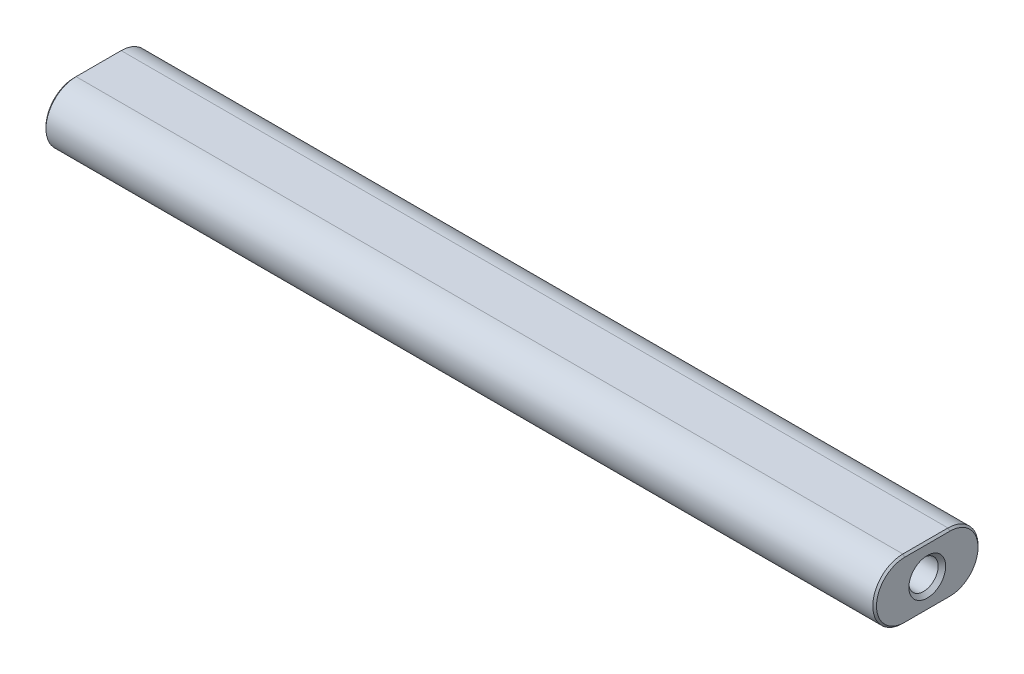
SolidWorks part; units mm, degrees
ref_plane "Front Plane" through (0, 0, 0) normal (0, 0, 1) x (1, 0, 0)
ref_plane "Top Plane" through (0, 0, 0) normal (0, 1, 0) x (1, 0, 0)
ref_plane "Right Plane" through (0, 0, 0) normal (1, 0, 0) x (0, 0, -1)
sketch "Sketch1" plane through (0, 0, 0) normal (1, 0, 0) x (0, 0, -1)
  line L0 (-3, 0) -> (3, 0) construction
  line L1 (-3, 4) -> (3, 4)
  line L2 (-3, -4) -> (3, -4)
  arc A0 (-3, 4) -> (-3, -4) centre (-3, 0) ccw
  arc A1 (3, -4) -> (3, 4) centre (3, 0) ccw
  point P2 (0, 0)
  dimension "D1" = 8
  dimension "D2" = 6
extrude "Boss-Extrude1" add sketch "Sketch1" along normal mid plane 110.5
sketch "Sketch2" plane through (55.25, 0, 0) normal (1, 0, 0) x (0, 0, -1)
  circle A0 centre (0, 0) radius 1.95
  dimension "D1" = 3.9
extrude "Cut-Extrude1" cut sketch "Sketch2" against normal blind 8
mirror "Mirror1" about plane through (0, 0, 0) normal (1, 0, 0) of "Cut-Extrude1"
chamfer "Chamfer1" distance 0.5 angle 45 2 edges at (-55.25, 0, -1.95) (55.25, 0, -1.95)
chamfer "Chamfer2" distance 0.25 angle 45 8 edges at (55.25, -4, 0) (55.25, 0, -7) (55.25, 0, 7) (55.25, 4, 0) (-55.25, -4, 0) (-55.25, 0, -7) (-55.25, 0, 7) (-55.25, 4, 0)
